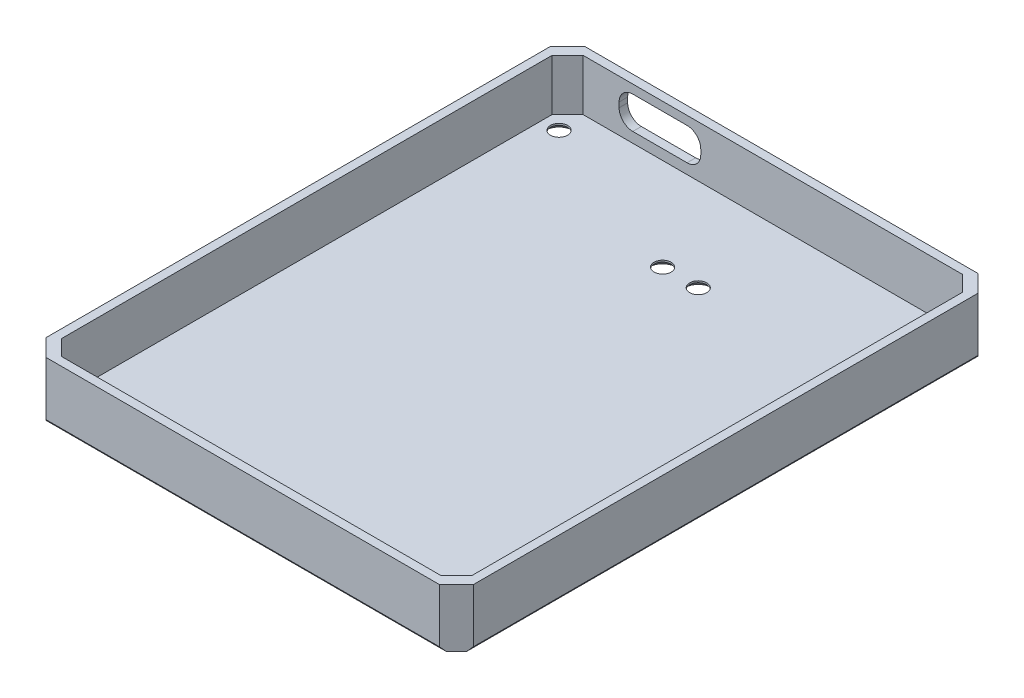
SolidWorks part; units mm, degrees
ref_plane "Front Plane" through (0, 0, 0) normal (0, 0, 1) x (1, 0, 0)
ref_plane "Top Plane" through (0, 0, 0) normal (0, 1, 0) x (1, 0, 0)
ref_plane "Right Plane" through (0, 0, 0) normal (1, 0, 0) x (0, 0, -1)
sketch "Sketch1" plane through (0, 0, 0) normal (0, 1, 0) x (1, 0, 0)
  line L1 (25, -31.5) -> (-25, -31.5)
  line L2 (25, -31.5) -> (25, 31.5)
  line L3 (25, 31.5) -> (-25, 31.5)
  line L4 (-25, -31.5) -> (-25, 31.5)
  line L5 (25, -31.5) -> (-25, 31.5) construction
  line L6 (25, 31.5) -> (-25, -31.5) construction
  line L7 (24, -30.5) -> (-24, -30.5)
  line L8 (24, -30.5) -> (24, 30.5)
  line L9 (24, 30.5) -> (-24, 30.5)
  line L10 (-24, -30.5) -> (-24, 30.5)
  line L11 (24, -30.5) -> (-24, 30.5) construction
  line L12 (24, 30.5) -> (-24, -30.5) construction
  point P0 (0, 0)
  point P6 (0, 0)
  dimension "D1" = 50
  dimension "D2" = 63
  dimension "D3" = 1
  dimension "D4" = 1
extrude "Boss-Extrude1" add sketch "Sketch1" along normal blind 6
sketch "Sketch2" plane through (0, 0, 0) normal (0, -1, 0) x (1, 0, 0)
  line L1 (-25, 31.5) -> (25, 31.5)
  line L2 (-25, 31.5) -> (-25, -31.5)
  line L3 (-25, -31.5) -> (25, -31.5)
  line L4 (25, 31.5) -> (25, -31.5)
  line L5 (-25, 31.5) -> (25, -31.5) construction
  line L6 (-25, -31.5) -> (25, 31.5) construction
  point P4 (0, 0)
extrude "Boss-Extrude2" add sketch "Sketch2" along normal blind 0.8
sketch "Sketch3" plane through (0, 0, 0) normal (0, 1, 0) x (1, 0, 0)
  line L0 (0, 31.5) -> (0, -31.5) construction
  line L1 (25, 31.5) -> (-25, 31.5) construction
  line L2 (-25, -31.5) -> (25, -31.5) construction
  line L4 (25, -31.5) -> (25, 31.5) construction
  line L5 (25, 0) -> (-25, 0) construction
  line L6 (-25, 31.5) -> (-25, -31.5) construction
  circle A1 centre (-22, 27.5) radius 1
  circle A11 centre (22, 27.5) radius 1
  circle A12 centre (22, -27.5) radius 1
  circle A13 centre (-22, -27.5) radius 1
  point P14 (-20.2161, 31.5)
  dimension "D2" = 4
  dimension "D1" = 3
  dimension "D3" = 2
extrude "Boss-Extrude3" add sketch "Sketch3" along normal up to surface (6 mm away) up to face at (0, 6, 0)
sketch "Sketch7" plane through (0, 0, 0) normal (0, 1, 0) x (1, 0, 0)
  line L0 (0, 0) -> (0, 61) construction
  line L2 (25, -31.5) -> (25, 31.5) construction
  line L3 (24, 30.5) -> (-24, 30.5)
  line L5 (24, -30.5) -> (-24, -30.5)
  line L6 (-24, 30.5) -> (-24, -30.5)
  line L7 (-25, 31.5) -> (-25, -31.5) construction
  line L8 (25, 31.5) -> (-25, 31.5) construction
  line L9 (-25, -31.5) -> (25, -31.5) construction
  line L10 (-24, -30.5) -> (24, -30.5) construction
  line L12 (24, 30.5) -> (24, -30.5)
  point P8 (-3.2725, 21.2153)
  dimension "D3" = 1
  dimension "D1" = 1
  dimension "D2" = 1
  dimension "D4" = 1
extrude "Cut-Extrude3" cut sketch "Sketch7" along normal blind 19.6
extrude "Cut-Extrude7" cut sketch "Sketch3<5>" against normal blind 10 contours A1 | A11 | A12 | A13 region at (-22, 0, -27.5) region at (22, 0, -27.5) region at (22, 0, 27.5) region at (-22, 0, 27.5)
sketch "Sketch3<5>" plane through (0, 0, 0) normal (0, 1, 0) x (1, 0, 0) same geometry as "Sketch3"
sketch "Sketch12" plane through (0, 0, 31.5) normal (0, 0, 1) x (1, 0, 0)
  line L0 (0, 20.5) -> (0, -0.8) construction
  line L1 (134.918, 6) -> (-11, 6)
  line L2 (134.918, 6) -> (134.918, 1)
  line L3 (134.918, 1) -> (-11, 1)
  line L4 (-11, 6) -> (-11, 1)
  line L5 (134.918, 6) -> (-11, 1) construction
  line L6 (134.918, 1) -> (-11, 6) construction
  line L8 (-11, 14.553) -> (-11, 6) construction
  line L9 (-134.918, 1) -> (11, 6) construction
  line L10 (-134.918, 6) -> (11, 1) construction
  line L11 (11, 6) -> (11, 1)
  line L12 (-134.918, 1) -> (11, 1)
  line L13 (-134.918, 6) -> (-134.918, 1)
  line L14 (-134.918, 6) -> (11, 6)
  line L15 (-25, 6) -> (25, 6) construction
  point P4 (61.959, 3.5)
  point P17 (-61.959, 3.5)
  dimension "D1" = 5
extrude "Boss-Extrude5" [suppressed] add sketch "Sketch12" along normal blind 6
chamfer "Chamfer6" [suppressed] distance 5 angle 20
mirror "Mirror14" [suppressed] about plane through (0, 0, 0) normal (0, 0, 1)
fillet "Fillet5" [suppressed] radius 6
sketch "Sketch14" plane through (0, 0, 0) normal (0, 1, 0) x (1, 0, 0)
  circle A0 centre (2.0845, 19.6974) radius 1
  circle A1 centre (-2.0845, 19.6974) radius 1
extrude "Cut-Extrude12" cut sketch "Sketch14" against normal blind 4.5
chamfer "Chamfer5" distance 0.6 angle 45 6 edges at (-22, -0.8, -28.5) (2.0845, -0.8, -20.6974) (-2.0845, -0.8, -20.6974) (-22, -0.8, 26.5) (22, -0.8, 26.5) (22, -0.8, -28.5)
chamfer "Chamfer8" [suppressed] distance 2 angle 40
chamfer "Chamfer7" distance 0.5 angle 40 4 edges at (25, -0.8, 0) (0, -0.8, 31.5) (-25, -0.8, 0) (0, -0.8, -31.5) first distance on face at (25, 2.6, 0) first distance on face at (0, 2.6, 31.5) first distance on face at (-25, 2.6, 0) first distance on face at (0, 2.6, -31.5)
chamfer "Chamfer9" distance 1.8 angle 45 4 edges at (-24, 3, 30.5) (24, 3, 30.5) (24, 3, -30.5) (-24, 3, -30.5)
chamfer "Chamfer10" distance 2 angle 45 4 edges at (25, 2.85, 31.5) (-25, 2.85, 31.5) (-25, 2.85, -31.5) (25, 2.85, -31.5)
sketch "Sketch15" plane through (0, 0, -31.5) normal (0, 0, -1) x (-1, 0, 0)
  line L1 (8.4234, 1.2004) -> (17.9734, 1.2004)
  line L2 (8.4234, 1.2004) -> (8.4234, 4.9804)
  line L3 (8.4234, 4.9804) -> (17.9734, 4.9804)
  line L4 (17.9734, 1.2004) -> (17.9734, 4.9804)
  line L5 (8.4234, 1.2004) -> (17.9734, 4.9804) construction
  line L6 (8.4234, 4.9804) -> (17.9734, 1.2004) construction
  line L8 (25, 6) -> (25, -0.3) construction
  line L9 (13.1984, 4.4107) -> (13.1984, 1.77) construction
  line L12 (13.1984, 1.77) -> (14.9984, 3.0904) construction
  line L14 (14.9984, 3.0904) -> (13.1984, 3.0904) construction
  point P4 (13.1984, 3.0904)
  point P22 (13.1984, 3.0904)
  dimension "D1" = 3.78
  dimension "D2" = 9.55
  dimension "D3" = 11.8016
extrude "Cut-Extrude13" cut sketch "Sketch15" against normal blind 10
fillet "Fillet6" radius 1.6 4 edges at (-8.4234, 4.9804, -31) (-8.4234, 1.2004, -31) (-17.9734, 1.2004, -31) (-17.9734, 4.9804, -31)
ref_plane "Plane1" through (-13.1984, 0, 0) normal (1, 0, 0) x (0, 0, -1)
